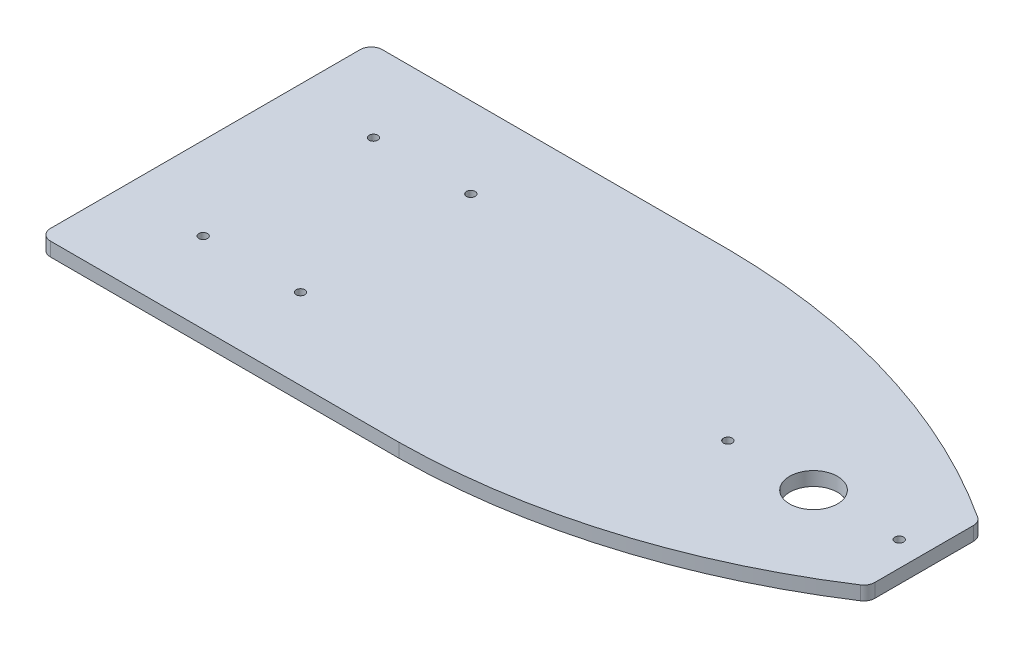
SolidWorks part; units mm, degrees
material "PLA"
ref_plane "Front" through (0, 0, 0) normal (0, 0, 1) x (1, 0, 0)
ref_plane "Top" through (0, 0, 0) normal (0, 1, 0) x (1, 0, 0)
ref_plane "Right" through (0, 0, 0) normal (1, 0, 0) x (0, 0, -1)
sketch "Sketch1" plane through (0, 0, 0) normal (0, 1, 0) x (1, 0, 0)
  line L1 (82.55, -38.1) -> (-82.55, -38.1)
  line L2 (82.55, -38.1) -> (82.55, 38.1)
  line L3 (82.55, 38.1) -> (-82.55, 38.1)
  line L4 (-82.55, -38.1) -> (-82.55, 38.1)
  line L5 (82.55, -38.1) -> (-82.55, 38.1) construction
  line L6 (82.55, 38.1) -> (-82.55, -38.1) construction
  point P0 (0, 0)
  dimension "D1" = 76.2
  dimension "D2" = 165.1
extrude "Boss-Extrude1" add sketch "Sketch1" along normal blind 3.175
sketch "Sketch4" plane through (0, 3.175, 0) normal (0, 1, 0) x (1, 0, 0)
  line L1 (82.55, -38.1) -> (0, -38.1)
  line L2 (82.55, 38.1) -> (82.55, 12.7)
  line L3 (82.55, -38.1) -> (82.55, 38.1) construction
  line L4 (82.55, -38.1) -> (82.55, -12.7)
  line L7 (82.55, 38.1) -> (0, 38.1)
  line L8 (0, -1.7463) -> (0, 1.7463) construction
  line L9 (-82.55, -38.1) -> (82.55, -38.1) construction
  arc A1 (0, 38.1) -> (82.55, 12.7) centre (-1.7067, -114.2904) cw
  arc A2 (0, -38.1) -> (82.55, -12.7) centre (-1.7067, 114.2904) ccw
  dimension "D3" = 152.4
  dimension "D4" = 152.4
  dimension "D1" = 25.4
  dimension "D2" = 25.4
extrude "Cut-Extrude1" cut sketch "Sketch4" against normal blind 3.175
fillet "Fillet3" radius 2.54 2 edges at (-82.55, 1.5875, 38.1) (-82.55, 1.5875, -38.1)
sketch "Sketch5" plane through (0, 3.175, 0) normal (0, 1, 0) x (1, 0, 0)
  line L0 (-1.7463, 0) -> (1.7463, 0) construction
  line L1 (82.55, -12.7) -> (82.55, 12.7) construction
  circle A0 centre (57.15, 0) radius 5.5
  dimension "D1" = 11
  dimension "D2" = 25.4
extrude "Cut-Extrude2" cut sketch "Sketch5" against normal blind 3.175
sketch "Sketch6" plane through (0, 3.175, 0) normal (0, 1, 0) x (1, 0, 0)
  line L1 (-63.5, 19.558) -> (-63.5, 0)
  line L2 (-63.5, -19.558) -> (-40.128, -19.558)
  line L4 (-24.13, 17.526) -> (-24.13, 16.5227)
  line L5 (-1.7463, 0) -> (1.7463, 0) construction
  line L6 (-63.5, 0) -> (-63.5, -19.558)
  line L7 (-43.815, -19.558) -> (-40.128, -19.558)
  circle A5 centre (-63.5, 19.558) radius 1.0033
  circle A8 centre (-63.5, -19.558) radius 1.0033
  circle A11 centre (-41.1313, -19.558) radius 1.0033
  circle A12 centre (-41.1313, 19.558) radius 1.0033
  dimension "D1" = 19.558
  dimension "D2" = 2.0066
  dimension "D8" = 2.0066
  dimension "D6" = 2.0066
  dimension "D3" = 19.558
sketch "Sketch7" plane through (0, 3.175, 0) normal (0, 1, 0) x (1, 0, 0)
  line L0 (57.15, -5.5) -> (57.15, 5.5)
  line L1 (57.15, 0) -> (76.835, 0)
  line L2 (-1.7463, 0) -> (1.7463, 0) construction
  line L3 (57.15, 0) -> (37.465, 0)
  circle A0 centre (57.15, 0) radius 5.5 construction
  circle A1 centre (76.835, 0) radius 1.0033
  circle A2 centre (37.465, 0) radius 1.0033
  dimension "D3" = 2.0066
  dimension "D4" = 2.0066
  dimension "D1" = 19.685
  dimension "D2" = 19.685
extrude "Cut-Extrude4" cut sketch "Sketch7" against normal through all contours A2 | A1 region at (36.4901, 3.175, 0)
extrude "Cut-Extrude5" cut sketch "Sketch6" against normal through all contours A5 | A8 | L2 A8 L6 | L4 L7 | L7 A11 | L7 A11 | A12 region at (-41.1313, 3.175, 19.1322) region at (-41.1313, 3.175, 19.9838) region at (-63.0742, 3.175, 19.1322) region at (-63.6419, 3.175, 19.6999) region at (-64.1894, 3.175, -20.2474) region at (-41.1313, 3.175, -19.558)
fillet "Fillet4" radius 2.54 2 edges at (82.55, 1.5875, 12.7) (82.55, 1.5875, -12.7)
